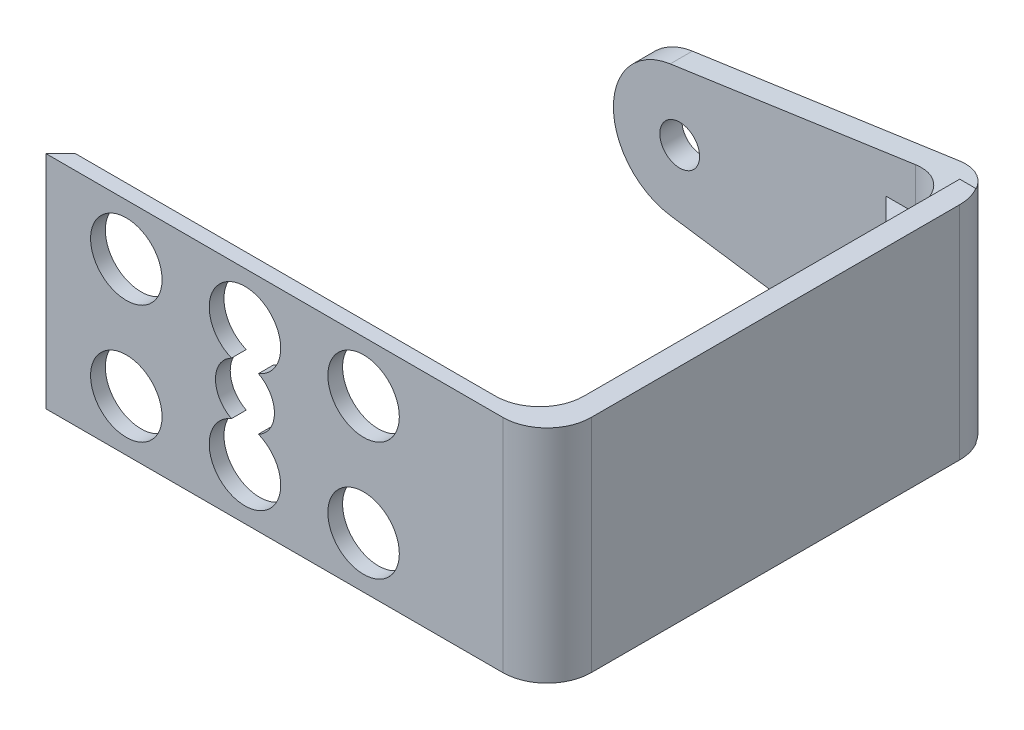
SolidWorks part; units mm, degrees
ref_plane "前视基准面" through (0, 0, 0) normal (0, 0, 1) x (1, 0, 0)
ref_plane "上视基准面" through (0, 0, 0) normal (0, 1, 0) x (1, 0, 0)
ref_plane "右视基准面" through (0, 0, 0) normal (1, 0, 0) x (0, 0, -1)
sketch "草图1" plane through (0, 0, 0) normal (0, 0, 1) x (1, 0, 0)
  line L1 (-13.5, -7.5) -> (13.5, -7.5)
  line L2 (-13.5, -7.5) -> (-13.5, 7.5)
  line L3 (-13.5, 7.5) -> (13.5, 7.5)
  line L4 (13.5, -7.5) -> (13.5, 7.5)
  line L5 (-13.5, -7.5) -> (13.5, 7.5) construction
  line L6 (-13.5, 7.5) -> (13.5, -7.5) construction
  point P0 (0, 0)
  dimension "D1" = 27
  dimension "D2" = 15
extrude "凸台-拉伸1" add sketch "草图1" along normal blind 1
sketch "草图2" plane through (0, 0, 1) normal (0, 0, 1) x (1, 0, 0)
  line L0 (-8.05, 4.025) -> (8.05, 4.025) construction
  line L3 (0, 1.6) -> (0, -1.6) construction
  line L4 (8.05, 4.025) -> (8.05, -4.025) construction
  line L5 (8.05, -4.025) -> (-8.05, -4.025) construction
  line L6 (-8.05, -4.025) -> (-8.05, 4.025) construction
  circle A0 centre (0, 4.025) radius 2.425
  circle A1 centre (0, -4.025) radius 2.425
  circle A2 centre (8.05, 4.025) radius 2.425
  circle A3 centre (8.05, -4.025) radius 2.425
  circle A4 centre (-8.05, 4.025) radius 2.425
  circle A5 centre (-8.05, -4.025) radius 2.425
  point P2 (0, 1.6)
  point P5 (0, -1.6)
  point P6 (0, 0)
  point P11 (-2.425, 4.025)
  point P20 (-5.625, 4.025)
  dimension "D1" = 4.85
  dimension "D4" = 3.2
  dimension "D2" = 3.2
extrude "切除-拉伸1" cut sketch "草图2" against normal through all
sketch "草图3" plane through (0, -7.5, 0) normal (0, -1, 0) x (1, 0, 0)
  line L0 (13.5, 0) -> (19, 0)
  line L1 (13.5, 1) -> (13.5, 0)
  line L2 (20.5, 1) -> (13.5, 1)
  line L3 (20.5, 1) -> (20.5, -30)
  line L5 (19, -28.5) -> (19, 0)
  line L6 (-4.5, -28.5) -> (-4.5, -30)
  line L7 (-4.5, -30) -> (20.5, -30)
  line L9 (-4.5, -28.5) -> (19, -28.5)
  dimension "D1" = 7
  dimension "D2" = 1.5
  dimension "D3" = 1.5
  dimension "D4" = 30
  dimension "D5" = 25
extrude "凸台-拉伸2" add sketch "草图3" against normal up to surface (15 mm away) up to face at (0, 7.5, 0.5)
sketch "草图6" plane through (0, 0, 0) normal (0, 1, 0) x (1, 0, 0)
  line L0 (19, 0) -> (19, 5)
  line L1 (19, 28.5) -> (19, 0) construction
  line L2 (19, 5) -> (14, 0)
  line L3 (19, 0) -> (-13.5, 0) construction
  line L4 (14, 0) -> (19, 0)
  line L5 (19, 28.5) -> (14, 28.5)
  line L6 (-4.5, 28.5) -> (19, 28.5) construction
  line L7 (14, 28.5) -> (19, 23.5)
  line L8 (19, 23.5) -> (19, 28.5)
  line L9 (20.5, 30) -> (-4.5, 30) construction
  line L10 (19, 19) -> (17.5, 19)
  line L11 (19, 19) -> (19, 21)
  line L12 (19, 21) -> (17.5, 21)
  line L13 (17.5, 19) -> (17.5, 21)
  point P18 (17.5, 20)
  dimension "D1" = 5
  dimension "D2" = 5
  dimension "D3" = 5
  dimension "D4" = 5
  dimension "D5" = 10
  dimension "D6" = 1.5
  dimension "D7" = 2
extrude "凸台-拉伸3" add sketch "草图6" along normal mid plane 8
sketch "草图7" plane through (0, 0, -30) normal (0, 0, -1) x (-1, 0, 0)
  line L0 (0.6417, -4.454) -> (-20.5, -7.5)
  line L1 (-20.5, 7.5) -> (-20.5, -7.5) construction
  line L2 (4.5, -7.5) -> (-20.5, -7.5) construction
  line L3 (-20.5, -7.5) -> (-20.5, 7.5)
  line L4 (-20.5, 7.5) -> (0.6417, 4.454)
  line L5 (4.5, -7.5) -> (-20.5, -7.5)
  line L6 (4.5, -7.5) -> (4.5, 7.5)
  line L7 (4.5, 7.5) -> (-20.5, 7.5)
  circle A0 centre (0, 0) radius 1.35
  circle A1 centre (0, 0) radius 4.5
  line M3 (4.5, 7.5) -> (-20.5, 7.5)
  line M5 (-20.5, -7.5) -> (4.5, -7.5)
  line M6 (4.5, -7.5) -> (4.5, 7.5)
  dimension "D1" = 2.7
extrude "切除-拉伸3" cut sketch "草图7" against normal up to surface (1.5 mm away) contours A1 L0 M5 M6 | A1 L6 L4 M3 | A0 region at (3.353, -6.0984, -30) region at (3.353, 6.0984, -30) region at (0, 0, -30) up to face at (11.875, 0, -28.5)
fillet "圆角1" radius 3 6 edges at (20.5, 0, -30) (20.5, 0, 1) (19, 5.75, 0) (19, -5.75, 0) (19, 5.6419, -28.5) (19, -5.6419, -28.5)
chamfer "倒角1" distance 1 angle 45 1 edges at (-13.5, 0, 0)
sketch "草图8" plane through (0, 0, 0) normal (0, 0, -1) x (-1, 0, 0)
  circle A0 centre (0, 0) radius 2
  dimension "D1" = 4
extrude "切除-拉伸4" cut sketch "草图8" against normal up to next
